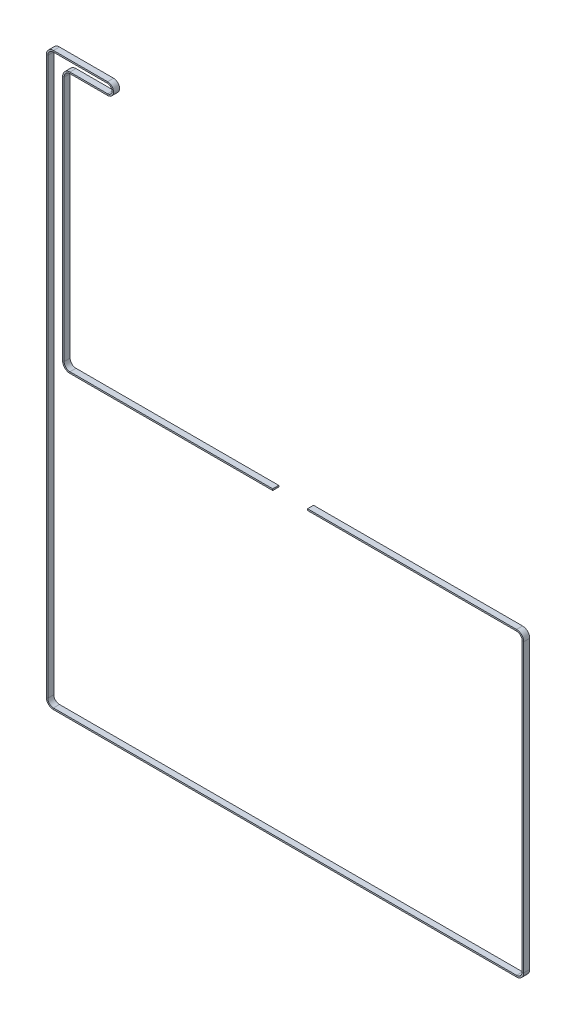
SolidWorks part; units mm, degrees
ref_plane "Front" through (0, 0, 0) normal (0, 0, 1) x (1, 0, 0)
ref_plane "Top" through (0, 0, 0) normal (0, 1, 0) x (1, 0, 0)
ref_plane "Right" through (0, 0, 0) normal (1, 0, 0) x (0, 0, -1)
sketch "Sketch1" plane through (0, -21, 4.45) normal (0, 0, 1) x (1, 0, 0)
  line L0 (10, 63.3) -> (47.5, 63.3)
  line L1 (47.5, 73.7) -> (-6.5, 73.7)
  line L2 (-12.875, 67.325) -> (-12.875, -488)
  line L3 (-6.5, -494.375) -> (455.5, -494.375)
  line L4 (461.875, -488) -> (461.875, -201.8969)
  line L5 (455.5, -195.5219) -> (246.9785, -195.5219)
  line L6 (212.2785, -199.0719) -> (212.2785, -194.0719) construction
  line L7 (3.4, 56.7) -> (3.4, -189.0719)
  line L8 (10, -195.6719) -> (212.2785, -195.6719)
  line L11 (246.9785, -194.6719) -> (246.9785, -191.0719) construction
  circle A0 centre (47.5, 68.5) radius 5.2 construction
  circle A1 centre (10, 56.7) radius 6.6 construction
  circle A2 centre (-6.5, 67.325) radius 6.375 construction
  circle A4 centre (-6.5, -488) radius 6.375 construction
  circle A5 centre (455.5, -488) radius 6.375 construction
  arc A7 (47.5, 73.7) -> (47.5, 63.3) centre (47.5, 68.5) cw
  arc A8 (10, 63.3) -> (3.4, 56.7) centre (10, 56.7) ccw
  arc A9 (-12.875, 67.325) -> (-6.5, 73.7) centre (-6.5, 67.325) cw
  arc A10 (-6.5, -494.375) -> (-12.875, -488) centre (-6.5, -488) cw
  arc A11 (455.5, -494.375) -> (461.875, -488) centre (455.5, -488) ccw
  arc A12 (461.875, -201.8969) -> (455.5, -195.5219) centre (455.5, -201.8969) ccw
  arc A13 (3.4, -189.0719) -> (10, -195.6719) centre (10, -189.0719) ccw
  circle A14 centre (-6.5, 67.325) radius 9 construction
  circle A15 centre (10, -189.0719) radius 6.6 construction
  circle A16 centre (10, -189.0719) radius 5.9875 construction
  circle A17 centre (455.5, -201.8969) radius 6.375 construction
  circle A18 centre (455.5, -201.8969) radius 5.9875 construction
  dimension "D1" = 12.75
ref_plane "Plane1" through (246.9785, -216.5219, 4.45) normal (-1, 0, 0) x (0, 0, 1)
sketch "Sketch2" plane through (246.9785, -216.5219, 4.45) normal (-1, 0, 0) x (0, 0, 1)
  line L1 (-3, 0.75) -> (3, 0.75)
  line L2 (-3, 0.75) -> (-3, -0.75)
  line L3 (-3, -0.75) -> (3, -0.75)
  line L4 (3, 0.75) -> (3, -0.75)
  line L5 (-3, 0.75) -> (3, -0.75) construction
  line L6 (-3, -0.75) -> (3, 0.75) construction
  point P0 (0, 0)
  dimension "D1" = 6
  dimension "D2" = 1.5
sweep "Sweep1" add profiles "Sketch2" path "Sketch1"
